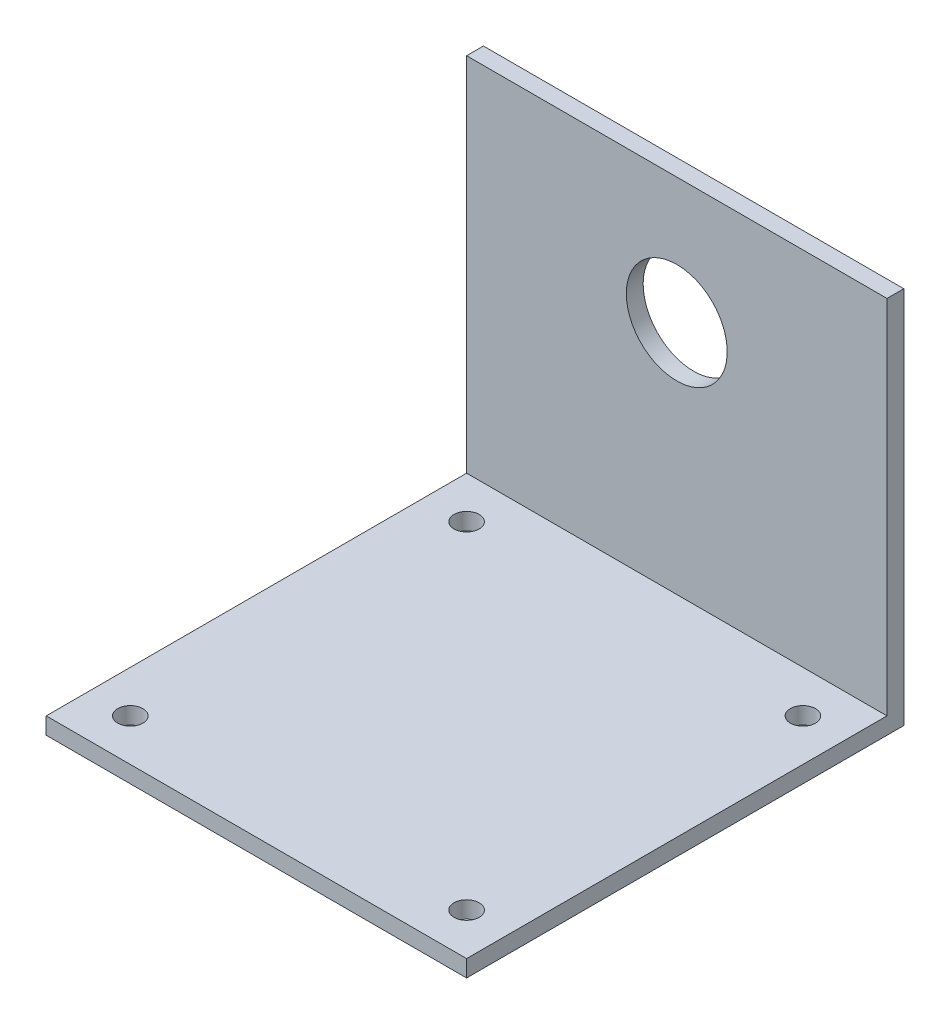
SolidWorks part; units mm, degrees
material "ABS PC"
ref_plane "Front Plane" through (0, 0, 0) normal (0, 0, 1) x (1, 0, 0)
ref_plane "Top Plane" through (0, 0, 0) normal (0, 1, 0) x (1, 0, 0)
ref_plane "Right Plane" through (0, 0, 0) normal (1, 0, 0) x (0, 0, -1)
sketch "Sketch1" plane through (0, 0, 0) normal (0, 1, 0) x (1, 0, 0)
  line L1 (0, 0) -> (50, 0)
  line L2 (0, 0) -> (0, -50)
  line L3 (0, -50) -> (50, -50)
  line L4 (50, 0) -> (50, -50)
  dimension "D1" = 50
  dimension "D2" = 50
extrude "Boss-Extrude1" add sketch "Sketch1" along normal blind 2
sketch "Sketch2" plane through (0, 0, 0) normal (0, 0, -1) x (-1, 0, 0)
  line L0 (-25, 45) -> (-25, 0) construction
  line L1 (-50, 0) -> (0, 0)
  line L2 (-50, 0) -> (-50, 45)
  line L3 (-50, 45) -> (0, 45)
  line L4 (0, 0) -> (0, 45)
  circle A0 centre (-25, 30) radius 6
  dimension "D3" = 12
  dimension "D1" = 50
  dimension "D2" = 45
  dimension "D4" = 15
extrude "Boss-Extrude2" add sketch "Sketch2" along normal blind 2
sketch "Sketch3" plane through (0, 2, 0) normal (0, 1, 0) x (1, 0, 0)
  line L0 (0, -25) -> (50, -25) construction
  line L1 (0, 0) -> (0, -50) construction
  line L2 (50, -50) -> (50, 0) construction
  line L4 (25, -50) -> (25, -25) construction
  line L5 (0, -50) -> (50, -50) construction
  circle A0 centre (45, -45) radius 1.5
  circle A1 centre (5, -45) radius 1.5
  circle A2 centre (45, -5) radius 1.5
  circle A3 centre (5, -5) radius 1.5
  dimension "D1" = 3
  dimension "D2" = 5
  dimension "D3" = 5
extrude "Cut-Extrude1" cut sketch "Sketch3" against normal blind 10
